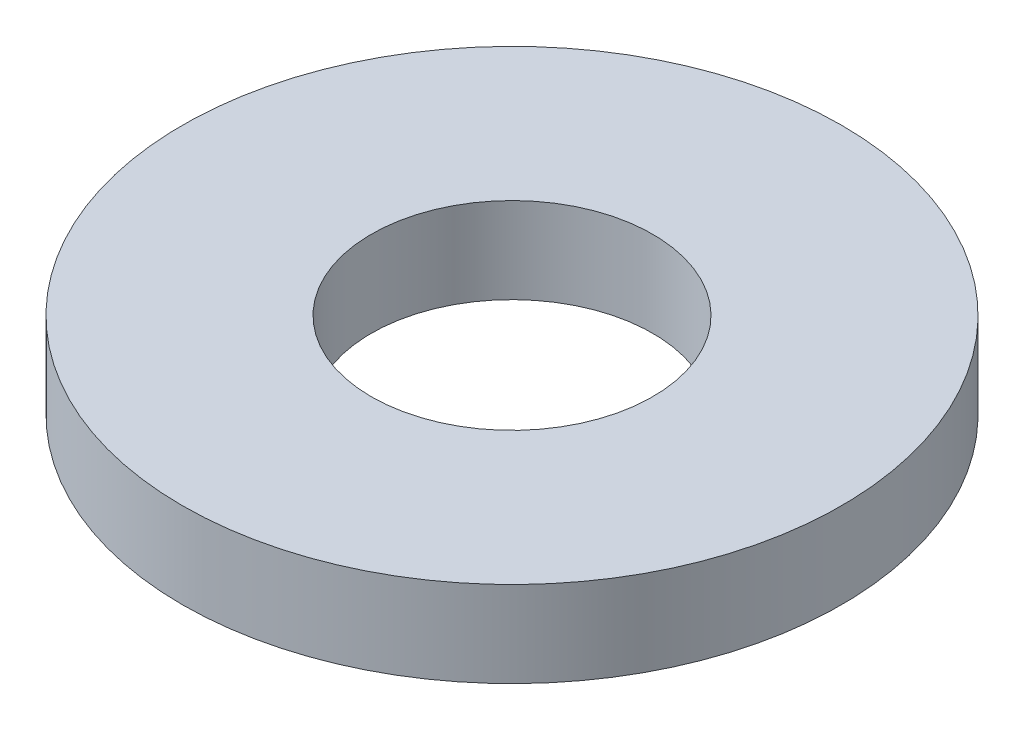
SolidWorks part; units mm, degrees
ref_plane "Front Plane" through (0, 0, 0) normal (0, 0, 1) x (1, 0, 0)
ref_plane "Top Plane" through (0, 0, 0) normal (0, 1, 0) x (1, 0, 0)
ref_plane "Right Plane" through (0, 0, 0) normal (1, 0, 0) x (0, 0, -1)
sketch "Sketch1" plane through (0, 0, 0) normal (0, 1, 0) x (1, 0, 0)
  circle A0 centre (0, 0) radius 2.05
  circle A1 centre (0, 0) radius 4.8
  dimension "D1" = 4.1
  dimension "D2" = 9.6
extrude "Boss-Extrude1" add sketch "Sketch1" along normal blind 0.625 and the other way blind 0.625
